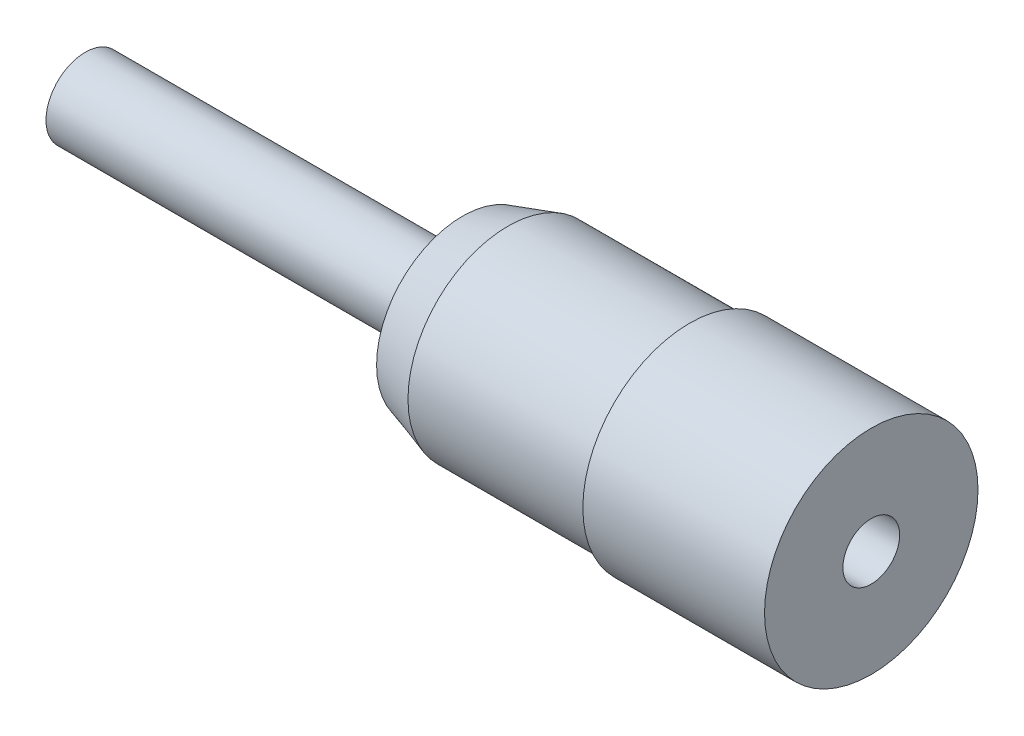
SolidWorks part; units mm, degrees
ref_plane "Front Plane" through (0, 0, 0) normal (0, 0, 1) x (1, 0, 0)
ref_plane "Top Plane" through (0, 0, 0) normal (0, 1, 0) x (1, 0, 0)
ref_plane "Right Plane" through (0, 0, 0) normal (1, 0, 0) x (0, 0, -1)
sketch "Sketch2" plane through (0, 0, 0) normal (0, 0, 1) x (1, 0, 0)
  line L0 (277.539, 63.4078) -> (314.539, 63.3714) construction
  line L1 (276.2601, 76.7069) -> (312.0557, 76.7069) construction
  line L2 (296.0557, 81.1069) -> (303.8557, 81.1069)
  line L3 (303.8557, 81.1069) -> (304.0557, 81.4069)
  line L4 (304.0557, 81.4069) -> (312.0557, 81.4069)
  line L5 (312.0557, 81.4069) -> (312.0557, 79.4069)
  line L6 (294.0557, 80.4888) -> (294.0557, 80.1748)
  line L7 (296.0557, 81.1069) -> (294.0557, 80.4888)
  line L8 (294.0469, 78.4369) -> (309.4469, 78.4369)
  line L9 (277.4469, 76.7069) -> (277.4469, 78.4369)
  line L10 (277.4469, 78.4369) -> (294.0469, 78.4369)
  line L11 (296.101, 80.8069) -> (294.0557, 80.1748)
  line L12 (296.101, 80.8069) -> (304.0162, 80.8069)
  line L13 (304.0162, 80.8069) -> (304.2162, 81.1069)
  line L14 (304.2162, 81.1069) -> (309.4469, 81.1069)
  line L15 (312.0557, 79.4069) -> (312.0557, 76.7069)
  line L16 (314.0469, 76.7069) -> (315.4863, 76.7069) construction
  line L17 (304.2162, 81.1069) -> (312.0557, 81.1069) construction
  line L18 (296.101, 80.8069) -> (294.1443, 80.2021) construction
  line L19 (309.4469, 78.4369) -> (309.4469, 81.1069)
  line L21 (277.4469, 76.7069) -> (312.0557, 76.7069)
  dimension "D6" = 2
  dimension "D1" = 37
  dimension "D2" = 4.7
  dimension "D3" = 4.4
  dimension "D7" = 1.73
  dimension "D8" = 18
  dimension "D9" = 2
  dimension "D10" = 15.4
  dimension "D11" = 0.2
  dimension "D12" = 8
  dimension "D13" = 0.3
revolve "Revolve4" add sketch "Sketch2" angle 360 about L21 region at (296.9188, 78.0474, 0)
hole_wizard "Tap Drill for M3 Tap1" positions "Sketch4" profile "Sketch3" hole size "M3" standard "ISO"
sketch "Sketch4" plane through (312.0557, 0, 0) normal (1, 0, 0) x (0, 0, -1)
  point P0 (0, 76.7069)
sketch "Sketch3" plane through (312.0557, 76.7069, 0) normal (0, 1, 0) x (0, 0, -1)
  line L0 (0, 0) -> (0, 6.2511)
  line L1 (0, 6.2511) -> (1.25, 5.5)
  line L2 (1.25, 5.5) -> (1.25, 0)
  line L5 (1.25, 0) -> (0, 0)
  line L10 (0, 6.2511) -> (-1.25, 5.5) construction
  line L11 (0, -6.35) -> (0, 107.95) construction
  dimension "Hole Dia." = 2.5
  dimension "Hole Depth" = 5.5
  dimension "Drill Angle" = 118
